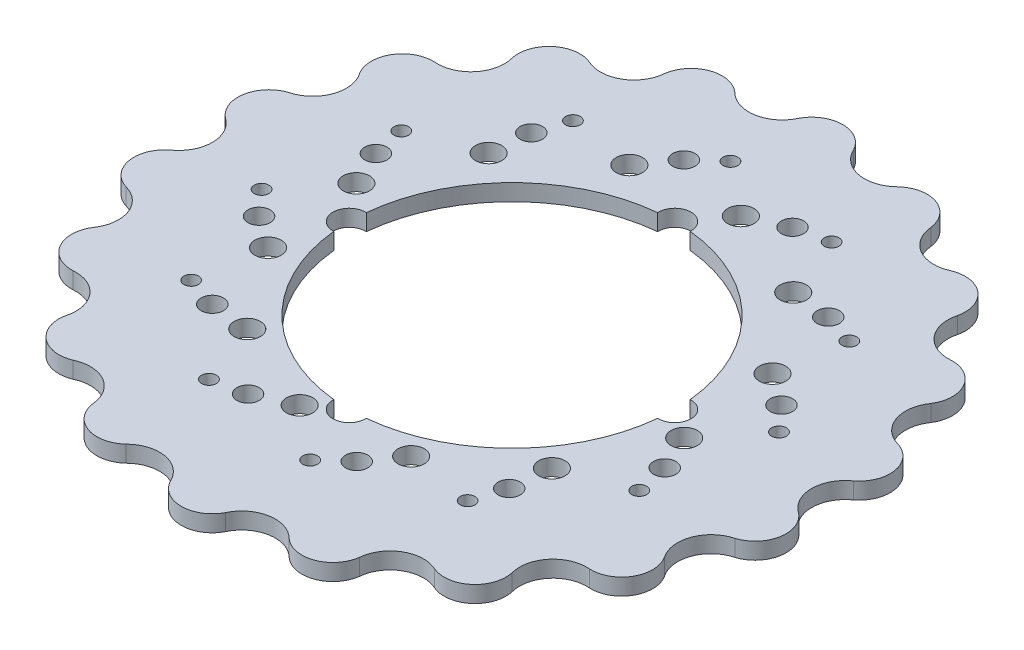
SolidWorks part; units mm, degrees
ref_plane "Front Plane" through (0, 0, 0) normal (0, 0, 1) x (1, 0, 0)
ref_plane "Top Plane" through (0, 0, 0) normal (0, 1, 0) x (1, 0, 0)
ref_plane "Right Plane" through (0, 0, 0) normal (1, 0, 0) x (0, 0, -1)
sketch "Sketch2" plane through (0, 0, 0) normal (0, 1, 0) x (1, 0, 0)
  line L0 (0, 0) -> (0, 101.6) construction
  line L1 (0, 0) -> (34.7492, 95.4728) construction
  line L2 (0, 0) -> (17.6427, 100.0565) construction
  line L3 (0, 0) -> (8.855, 101.2134) construction
  line L4 (26.296, 98.1381) -> (0, 0) construction
  circle A0 centre (0, 0) radius 101.6
  circle A1 centre (0, 0) radius 92.075
  circle A2 centre (0, 0) radius 96.8375
  arc A3 (0, 101.6) -> (8.4399, 96.469) centre (0, 92.0931) cw
  arc A4 (8.4399, 96.469) -> (15.9887, 90.6762) centre (17.7777, 100.8223) ccw
  arc A5 (25.0634, 93.5378) -> (15.9887, 90.6762) centre (17.7777, 100.8223) cw
  arc A6 (34.7492, 95.4728) -> (25.0634, 93.5378) centre (31.4977, 86.5392) ccw
  arc A7 (34.7492, 95.4728) -> (40.9253, 87.7646) centre (31.4977, 86.5392) cw
  arc A8 (40.9253, 87.7646) -> (46.0375, 79.7393) centre (51.1888, 88.6617) ccw
  arc A9 (55.5437, 79.3246) -> (46.0375, 79.7393) centre (51.1888, 88.6617) cw
  arc A10 (65.3072, 77.8301) -> (55.5437, 79.3246) centre (59.1963, 70.5474) ccw
  arc A11 (65.3072, 77.8301) -> (68.4745, 68.4745) centre (59.1963, 70.5474) cw
  arc A12 (68.4745, 68.4745) -> (70.5335, 59.1847) centre (78.4258, 65.8071) ccw
  arc A13 (79.3246, 55.5437) -> (70.5335, 59.1847) centre (78.4258, 65.8071) cw
  arc A14 (87.9882, 50.8) -> (79.3246, 55.5437) centre (79.755, 46.0465) ccw
  arc A15 (87.9882, 50.8) -> (87.7646, 40.9253) centre (79.755, 46.0465) cw
  arc A16 (87.7646, 40.9253) -> (86.5222, 31.4915) centre (96.2035, 35.0152) ccw
  arc A17 (93.5378, 25.0634) -> (86.5222, 31.4915) centre (96.2035, 35.0152) cw
  arc A18 (100.0565, 17.6427) -> (93.5378, 25.0634) centre (90.694, 15.9918) ccw
  arc A19 (100.0565, 17.6427) -> (96.469, 8.4399) centre (90.694, 15.9918) cw
  arc A20 (96.469, 8.4399) -> (92.075, 0) centre (102.3777, 0) ccw
  arc A21 (96.469, -8.4399) -> (92.075, 0) centre (102.3777, 0) cw
  arc A22 (100.0565, -17.6427) -> (96.469, -8.4399) centre (90.694, -15.9918) ccw
  arc A23 (100.0565, -17.6427) -> (93.5378, -25.0634) centre (90.694, -15.9918) cw
  arc A24 (93.5378, -25.0634) -> (86.5222, -31.4915) centre (96.2035, -35.0152) ccw
  arc A25 (87.7646, -40.9253) -> (86.5222, -31.4915) centre (96.2035, -35.0152) cw
  arc A26 (87.9882, -50.8) -> (87.7646, -40.9253) centre (79.755, -46.0465) ccw
  arc A27 (87.9882, -50.8) -> (79.3246, -55.5437) centre (79.755, -46.0465) cw
  arc A28 (79.3246, -55.5437) -> (70.5335, -59.1847) centre (78.4258, -65.8071) ccw
  arc A29 (68.4745, -68.4745) -> (70.5335, -59.1847) centre (78.4258, -65.8071) cw
  arc A30 (65.3072, -77.8301) -> (68.4745, -68.4745) centre (59.1963, -70.5474) ccw
  arc A31 (65.3072, -77.8301) -> (55.5437, -79.3246) centre (59.1963, -70.5474) cw
  arc A32 (55.5437, -79.3246) -> (46.0375, -79.7393) centre (51.1888, -88.6617) ccw
  arc A33 (40.9253, -87.7646) -> (46.0375, -79.7393) centre (51.1888, -88.6617) cw
  arc A34 (34.7492, -95.4728) -> (40.9253, -87.7646) centre (31.4977, -86.5392) ccw
  arc A35 (34.7492, -95.4728) -> (25.0634, -93.5378) centre (31.4977, -86.5392) cw
  arc A36 (25.0634, -93.5378) -> (15.9887, -90.6762) centre (17.7777, -100.8223) ccw
  arc A37 (8.4399, -96.469) -> (15.9887, -90.6762) centre (17.7777, -100.8223) cw
  arc A38 (0, -101.6) -> (8.4399, -96.469) centre (0, -92.0931) ccw
  arc A39 (0, -101.6) -> (-8.4399, -96.469) centre (0, -92.0931) cw
  arc A40 (-8.4399, -96.469) -> (-15.9887, -90.6762) centre (-17.7777, -100.8223) ccw
  arc A41 (-25.0634, -93.5378) -> (-15.9887, -90.6762) centre (-17.7777, -100.8223) cw
  arc A42 (-34.7492, -95.4728) -> (-25.0634, -93.5378) centre (-31.4977, -86.5392) ccw
  arc A43 (-34.7492, -95.4728) -> (-40.9253, -87.7646) centre (-31.4977, -86.5392) cw
  arc A44 (-40.9253, -87.7646) -> (-46.0375, -79.7393) centre (-51.1888, -88.6617) ccw
  arc A45 (-55.5437, -79.3246) -> (-46.0375, -79.7393) centre (-51.1888, -88.6617) cw
  arc A46 (-65.3072, -77.8301) -> (-55.5437, -79.3246) centre (-59.1963, -70.5474) ccw
  arc A47 (-65.3072, -77.8301) -> (-68.4745, -68.4745) centre (-59.1963, -70.5474) cw
  arc A48 (-68.4745, -68.4745) -> (-70.5335, -59.1847) centre (-78.4258, -65.8071) ccw
  arc A49 (-79.3246, -55.5437) -> (-70.5335, -59.1847) centre (-78.4258, -65.8071) cw
  arc A50 (-87.9882, -50.8) -> (-79.3246, -55.5437) centre (-79.755, -46.0465) ccw
  arc A51 (-87.9882, -50.8) -> (-87.7646, -40.9253) centre (-79.755, -46.0465) cw
  arc A52 (-87.7646, -40.9253) -> (-86.5222, -31.4915) centre (-96.2035, -35.0152) ccw
  arc A53 (-93.5378, -25.0634) -> (-86.5222, -31.4915) centre (-96.2035, -35.0152) cw
  arc A54 (-100.0565, -17.6427) -> (-93.5378, -25.0634) centre (-90.694, -15.9918) ccw
  arc A55 (-100.0565, -17.6427) -> (-96.469, -8.4399) centre (-90.694, -15.9918) cw
  arc A56 (-96.469, -8.4399) -> (-92.075, 0) centre (-102.3777, 0) ccw
  arc A57 (-96.469, 8.4399) -> (-92.075, 0) centre (-102.3777, 0) cw
  arc A58 (-100.0565, 17.6427) -> (-96.469, 8.4399) centre (-90.694, 15.9918) ccw
  arc A59 (-100.0565, 17.6427) -> (-93.5378, 25.0634) centre (-90.694, 15.9918) cw
  arc A60 (-93.5378, 25.0634) -> (-86.5222, 31.4915) centre (-96.2035, 35.0152) ccw
  arc A61 (-87.7646, 40.9253) -> (-86.5222, 31.4915) centre (-96.2035, 35.0152) cw
  arc A62 (-87.9882, 50.8) -> (-87.7646, 40.9253) centre (-79.755, 46.0465) ccw
  arc A63 (-87.9882, 50.8) -> (-79.3246, 55.5437) centre (-79.755, 46.0465) cw
  arc A64 (-79.3246, 55.5437) -> (-70.5335, 59.1847) centre (-78.4258, 65.8071) ccw
  arc A65 (-68.4745, 68.4745) -> (-70.5335, 59.1847) centre (-78.4258, 65.8071) cw
  arc A66 (-65.3072, 77.8301) -> (-68.4745, 68.4745) centre (-59.1963, 70.5474) ccw
  arc A67 (-65.3072, 77.8301) -> (-55.5437, 79.3246) centre (-59.1963, 70.5474) cw
  arc A68 (-55.5437, 79.3246) -> (-46.0375, 79.7393) centre (-51.1888, 88.6617) ccw
  arc A69 (-40.9253, 87.7646) -> (-46.0375, 79.7393) centre (-51.1888, 88.6617) cw
  arc A70 (-34.7492, 95.4728) -> (-40.9253, 87.7646) centre (-31.4977, 86.5392) ccw
  arc A71 (-34.7492, 95.4728) -> (-25.0634, 93.5378) centre (-31.4977, 86.5392) cw
  arc A72 (-25.0634, 93.5378) -> (-15.9887, 90.6762) centre (-17.7777, 100.8223) ccw
  arc A73 (-8.4399, 96.469) -> (-15.9887, 90.6762) centre (-17.7777, 100.8223) cw
  arc A74 (0, 101.6) -> (-8.4399, 96.469) centre (0, 92.0931) ccw
  point P10 (8.4399, 96.469)
  point P11 (25.0634, 93.5378)
  point P12 (15.9887, 90.6762)
  point P175 (0, 0)
  dimension "D1" = 203.2
  dimension "D2" = 184.15
  dimension "D5" = 193.675
  dimension "D4" = 18
  dimension "D3" = 20
  dimension "D6" = 5
  dimension "D7" = 5
extrude "Boss-Extrude1" add sketch "Sketch2" along normal blind 5.08 contours A67 A66 A2 | A68 A2 A65 A1 | A71 A70 A2 | A72 A2 A69 A1 | A2 A73 A1 A4 | A3 A74 A2 | A8 A2 A5 A1 | A7 A6 A2 | A11 A10 A2 | A12 A2 A9 A1 | A16 A2 A13 A1 | A15 A14 A2 | A20 A2 A17 A1 | A19 A18 A2 | A24 A2 A21 A1 | A23 A22 A2 | A28 A2 A25 A1 | A27 A26 A2 | A32 A2 A29 A1 | A31 A30 A2 | A36 A2 A33 A1 | A35 A34 A2 | A40 A2 A37 A1 | A39 A38 A2 | A44 A2 A41 A1 | A43 A42 A2 | A48 A2 A45 A1 | A47 A46 A2 | A52 A2 A49 A1 | A51 A50 A2 | A1 | A55 A54 A2 | A59 A58 A2 | A63 A62 A2 | A64 A2 A61 A1 | A60 A2 A57 A1 | A56 A2 A53 A1 region at (97.2191, 0, -17.1424) region at (97.2191, 0, 17.1424) region at (85.4931, 0, -49.3595) region at (92.5977, 0, -16.3275) region at (85.4931, 0, 49.3595) region at (92.5977, 0, 16.3275) region at (63.4553, 0, -75.6231) region at (81.429, 0, -47.0131) region at (0, 0, 0) region at (63.4553, 0, 75.6231) region at (81.429, 0, 47.0131) region at (33.7639, 0, -92.7654) region at (60.4389, 0, -72.0282) region at (33.7639, 0, 92.7654) region at (60.4389, 0, 72.0282) region at (0, 0, -98.7189) region at (32.1588, 0, -88.3557) region at (0, 0, 98.7189) region at (32.1588, 0, 88.3557) region at (-33.7639, 0, -92.7654) region at (0, 0, -94.0262) region at (-33.7639, 0, 92.7654) region at (0, 0, 94.0262) region at (-63.4553, 0, -75.6231) region at (-32.1588, 0, -88.3557) region at (-63.4553, 0, 75.6231) region at (-32.1588, 0, 88.3557) region at (-85.4931, 0, -49.3595) region at (-60.4389, 0, -72.0282) region at (-85.4931, 0, 49.3595) region at (-60.4389, 0, 72.0282) region at (-97.2191, 0, -17.1424) region at (-81.429, 0, -47.0131) region at (-97.2191, 0, 17.1424) region at (-81.429, 0, 47.0131) region at (-92.5977, 0, -16.3275) region at (-92.5977, 0, 16.3275)
sketch "Sketch3" plane through (0, 5.08, 0) normal (0, 1, 0) x (1, 0, 0)
  circle A0 centre (0, 0) radius 50
  circle A1 centre (0, 50) radius 5
  circle A2 centre (50, 0) radius 5
  circle A3 centre (0, -50) radius 5
  circle A4 centre (-50, 0) radius 5
  point P13 (0, 0)
  dimension "D1" = 4
  dimension "D2" = 10
extrude "Cut-Extrude1" cut sketch "Sketch3" against normal through all contours A0 A1 | A0 A1 | A0 A4 | A0 A4 | A0 A2 | A0 A2 | A0 A3 | A0 A3 | A0 region at (47.8335, 5.08, 0) region at (52.0764, 5.08, 0) region at (0, 5.08, -47.8335) region at (0, 5.08, -52.0764) region at (0, 5.08, 52.0764) region at (0, 5.08, 47.8335) region at (-47.8335, 5.08, 0) region at (-52.0764, 5.08, 0)
sketch "Sketch4" plane through (0, 5.08, 0) normal (0, 1, 0) x (1, 0, 0)
  arc A0 (0, 55) -> (39.6875, 68.7408) centre (35.1097, 17.7778) cw construction
  circle A3 centre (8.7092, 61.6093) radius 4.0351
  circle A4 centre (19.6365, 66.5504) radius 3.4245
  circle A5 centre (29.5538, 68.6434) radius 2.2596
  circle A6 centre (37.077, 49.3409) radius 4.0351
  circle A7 centre (49.0109, 48.1563) radius 3.4245
  circle A8 centre (58.646, 45.0104) radius 2.2596
  circle A9 centre (55.5101, 24.5322) radius 4.0351
  circle A10 centre (65.2529, 17.5394) radius 3.4245
  circle A11 centre (72.0241, 9.9974) radius 2.2596
  circle A12 centre (59.0693, -6.1692) radius 4.0351
  circle A13 centre (64.0104, -17.0965) radius 3.4245
  circle A14 centre (66.1034, -27.0138) radius 2.2596
  circle A15 centre (46.8009, -34.537) radius 4.0351
  circle A16 centre (45.6163, -46.4709) radius 3.4245
  circle A17 centre (42.4704, -56.106) radius 2.2596
  circle A18 centre (21.9922, -52.9701) radius 4.0351
  circle A19 centre (14.9994, -62.7129) radius 3.4245
  circle A20 centre (7.4574, -69.4841) radius 2.2596
  circle A21 centre (-8.7092, -56.5293) radius 4.0351
  circle A22 centre (-19.6365, -61.4704) radius 3.4245
  circle A23 centre (-29.5538, -63.5634) radius 2.2596
  circle A24 centre (-37.077, -44.2609) radius 4.0351
  circle A25 centre (-49.0109, -43.0763) radius 3.4245
  circle A26 centre (-58.646, -39.9304) radius 2.2596
  circle A27 centre (-55.5101, -19.4522) radius 4.0351
  circle A28 centre (-65.2529, -12.4594) radius 3.4245
  circle A29 centre (-72.0241, -4.9174) radius 2.2596
  circle A30 centre (-59.0693, 11.2492) radius 4.0351
  circle A31 centre (-64.0104, 22.1765) radius 3.4245
  circle A32 centre (-66.1034, 32.0938) radius 2.2596
  circle A33 centre (-46.8009, 39.617) radius 4.0351
  circle A34 centre (-45.6163, 51.5509) radius 3.4245
  circle A35 centre (-42.4704, 61.186) radius 2.2596
  circle A36 centre (-21.9922, 58.0501) radius 4.0351
  circle A37 centre (-14.9994, 67.7929) radius 3.4245
  circle A38 centre (-7.4574, 74.5641) radius 2.2596
  point P7 (0, 0)
  point P16 (0, 0)
  point P83 (0, 2.54)
  dimension "D1" = 12
extrude "Cut-Extrude3" cut sketch "Sketch4" against normal through all
